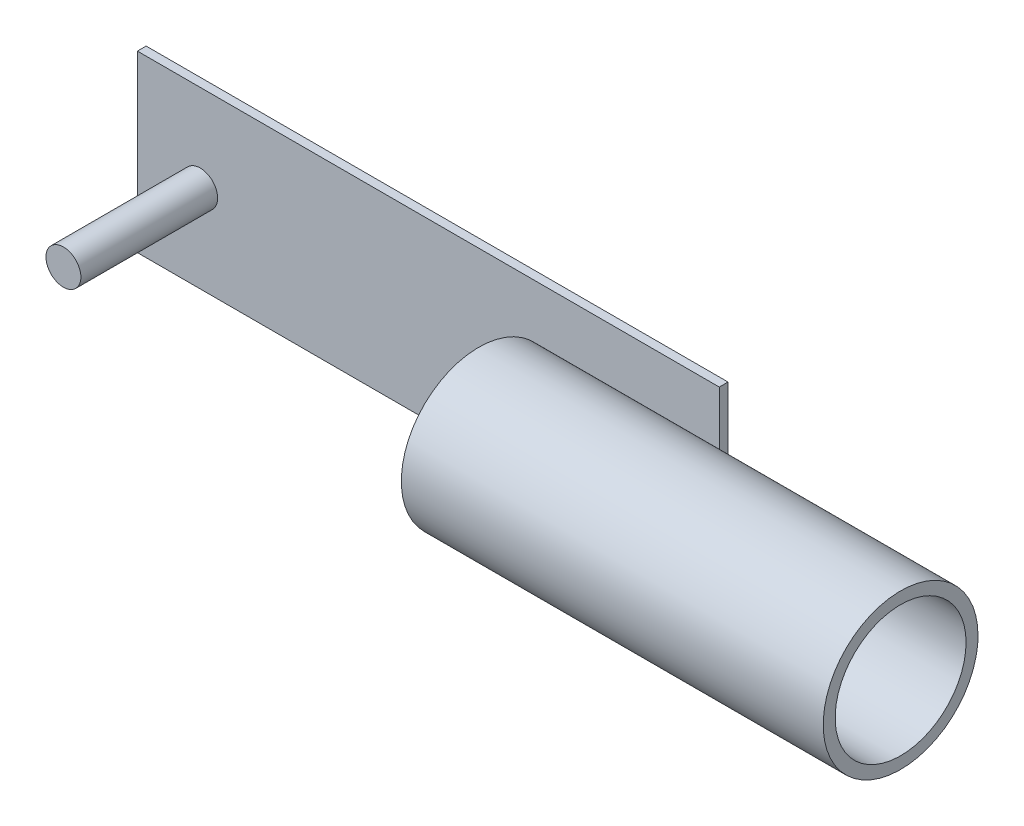
SolidWorks part; units mm, degrees
ref_plane "前视基准面" through (0, 0, 0) normal (0, 0, 1) x (1, 0, 0)
ref_plane "上视基准面" through (0, 0, 0) normal (0, 1, 0) x (1, 0, 0)
ref_plane "右视基准面" through (0, 0, 0) normal (1, 0, 0) x (0, 0, -1)
sketch "草图1" plane through (-45.881, 0, 0) normal (0, 0, 1) x (1, 0, 0)
  line L0 (-97.3029, 30) -> (-75.7214, 30)
  line L1 (-97.3029, 60) -> (102.6971, 60)
  line L2 (-97.3029, 60) -> (-97.3029, 0)
  line L3 (-97.3029, 0) -> (102.6971, 0)
  line L4 (102.6971, 60) -> (102.6971, 0)
  circle A0 centre (-75.7214, 30) radius 6
  dimension "D1" = 200
  dimension "D2" = 60
extrude "凸台-拉伸1" add sketch "草图1" along normal blind 3 contours A0 L2 L3 L4 L1 region at (-42.4378, 30, 0)
extrude "凸台-拉伸2" add sketch "草图1<3>" along normal blind 50 contours A0 region at (-121.6024, 35.8303, 0)
sketch "草图1<3>" plane through (-45.881, 0, 0) normal (0, 0, 1) x (1, 0, 0) same geometry as "草图1"
sketch "草图2" plane through (0, 0, 2.2689) normal (1, 0, 0) x (0, 0, -1)
  circle A0 centre (-26.6, 29.775) radius 22.5
  circle A1 centre (-26.6, 29.775) radius 26.6
  dimension "D1" = 45
extrude "凸台-拉伸3" add sketch "草图2" along normal blind 145
sketch "草图3" plane through (0, 0, 0) normal (1, 0, 0) x (0, 0, -1)
